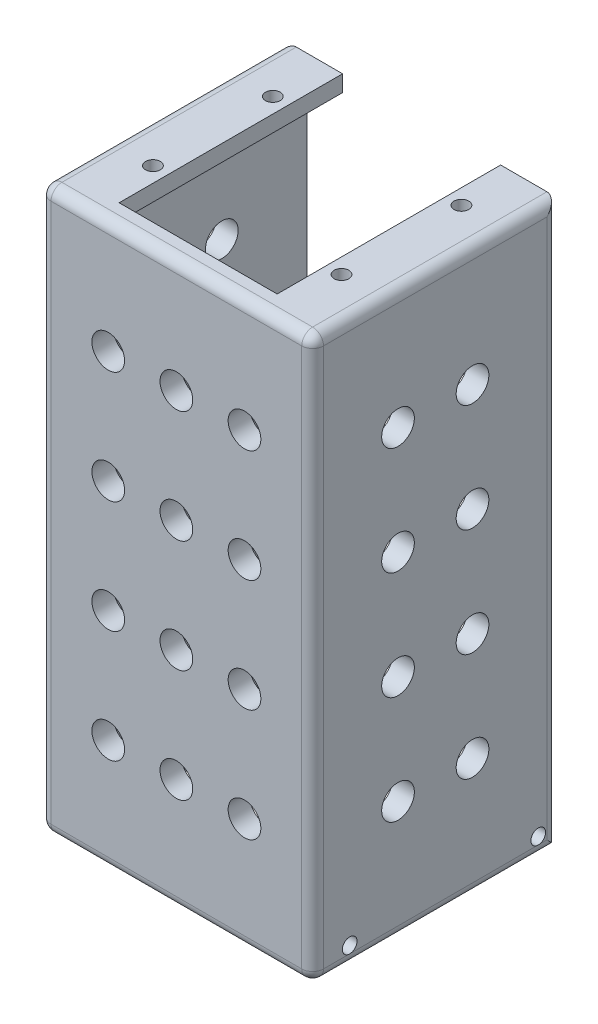
SolidWorks part; units mm, degrees
material "ABS PC"
ref_plane "Front Plane" through (0, 0, 0) normal (0, 0, 1) x (1, 0, 0)
ref_plane "Top Plane" through (0, 0, 0) normal (0, 1, 0) x (1, 0, 0)
ref_plane "Right Plane" through (0, 0, 0) normal (1, 0, 0) x (0, 0, -1)
sketch "Sketch2" plane through (0, 0, 0) normal (0, 1, 0) x (1, 0, 0)
  line L1 (25, -22.5) -> (-25, -22.5)
  line L2 (25, -22.5) -> (25, 22.5)
  line L3 (25, 22.5) -> (-25, 22.5)
  line L4 (-25, -22.5) -> (-25, 22.5)
  line L5 (25, -22.5) -> (-25, 22.5) construction
  line L6 (25, 22.5) -> (-25, -22.5) construction
  point P0 (0, 0)
extrude "Boss-Extrude1" add sketch "Sketch2" along normal blind 103
sketch "Sketch3" plane through (0, 103, 0) normal (0, 1, 0) x (1, 0, 0)
  line L0 (-21, 22.5) -> (-21, -18.5)
  line L1 (25, 22.5) -> (-25, 22.5) construction
  line L2 (-21, -18.5) -> (21, -18.5)
  line L3 (21, -18.5) -> (21, 22.5)
  line L4 (25, -22.5) -> (25, 22.5) construction
  line L5 (-25, 22.5) -> (-25, -22.5) construction
  line L6 (-25, -22.5) -> (25, -22.5) construction
  line L7 (-21, 22.5) -> (21, 22.5)
  dimension "D1" = 4
  dimension "D2" = 4
  dimension "D3" = 4
extrude "Cut-Extrude1" cut sketch "Sketch3" against normal blind 150
sketch "Sketch4" plane through (0, 103, 0) normal (0, 1, 0) x (1, 0, 0)
  line L0 (-25, -11.5) -> (-16, -11.5)
  line L1 (-25, 22.5) -> (-25, -22.5) construction
  line L2 (-16, -11.5) -> (-16, -6.5)
  line L3 (-16, -6.5) -> (-25, -6.5)
  line L4 (-25, -6.5) -> (-25, -11.5)
  line L5 (-21, -18.5) -> (21, -18.5) construction
  line L6 (-21, 22.5) -> (-21, -18.5) construction
  line L7 (0, -22.5) -> (0, 39.4349)
  line L8 (-25, -22.5) -> (25, -22.5) construction
  line L9 (25, -6.5) -> (25, -11.5)
  line L10 (25, -11.5) -> (16, -11.5)
  line L11 (16, -11.5) -> (16, -6.5)
  line L12 (16, -6.5) -> (25, -6.5)
  dimension "D1" = 7
  dimension "D2" = 12
  dimension "D3" = 5
extrude "Boss-Extrude4" [suppressed] add sketch "Sketch4" along normal blind 2 contours L2 L3 L4 L0 | L12 L9 L10 L11
sketch "Sketch6" plane through (0, 0, 22.5) normal (0, 0, 1) x (1, 0, 0)
  line L0 (-25, 103) -> (25, 103) construction
  line L1 (25, 103) -> (25, 0) construction
  circle A0 centre (12.5, 82.4) radius 3
  circle A1 centre (0, 82.4) radius 3
  circle A2 centre (-12.5, 82.4) radius 3
  circle A3 centre (-12.5, 61.8) radius 3
  circle A4 centre (0, 61.8) radius 3
  circle A5 centre (12.5, 61.8) radius 3
  circle A6 centre (12.5, 20.6) radius 3
  circle A7 centre (0, 20.6) radius 3
  circle A8 centre (-12.5, 20.6) radius 3
  circle A9 centre (-12.5, 41.2) radius 3
  circle A10 centre (0, 41.2) radius 3
  circle A11 centre (12.5, 41.2) radius 3
  dimension "D1" = 20.6
  dimension "D2" = 12.5
  dimension "D3" = 12.5
  dimension "D4" = 12.5
fillet "Fillet2" radius 2 7 edges at (0, 103, 22.5) (25, 51.5, 22.5) (0, 0, 22.5) (-25, 51.5, -22.5) (-25, 103, 0) (-25, 51.5, 22.5) (-25, 0, 0)
fillet "Fillet3" radius 2 5 edges at (24.4142, 0.5858, 21.9142) (24.4142, 102.4142, 21.9142) (25, 103, -1) (25, 51.5, -22.5) (25, 0, -1)
sketch "Sketch7" plane through (-21, 0, 0) normal (1, 0, 0) x (0, 0, -1)
  line L0 (-12.9, 0) -> (-12.9, 103)
  line L1 (22.5, 0) -> (-18.5, 0) construction
  line L2 (22.5, 103) -> (-18.5, 103) construction
  line L3 (-18.5, 0) -> (-18.5, 103) construction
  line L4 (16.1, 0) -> (16.1, 103)
  line L5 (21.7, 0) -> (21.7, 103)
  line L6 (-12.9, 103) -> (-18.5, 103)
  line L7 (-18.5, 103) -> (-18.5, 0)
  line L8 (-18.5, 0) -> (-29.6933, -0.9584)
  line L9 (-29.6933, -0.9584) -> (21.7, 0)
  line L10 (21.7, 103) -> (-18.5, 103)
  line L11 (-18.5, 30) -> (21.7, 30)
  line M9 (-18.5, 0) -> (22.5, 0)
  dimension "D1" = 5.6
  dimension "D2" = 29
  dimension "D3" = 5.6
  dimension "D4" = 1.068
  dimension "D5" = 30
extrude "Boss-Extrude6" add sketch "Sketch7" along normal blind 4 contours L11 L4 L5 M9 | L11 L7 L0 M9 region at (-21, 15, 15.7) region at (-21, 15, -18.9)
sketch "Sketch9" plane through (21, 0, 0) normal (-1, 0, 0) x (0, 0, 1)
  line L0 (12.9, 0) -> (12.9, 30)
  line L1 (18.5, 0) -> (-22.5, 0) construction
  line L2 (12.9, 30) -> (18.5, 30)
  line L3 (18.5, 0) -> (18.5, 103) construction
  line L4 (18.5, 30) -> (18.5, 0)
  line L5 (18.5, 0) -> (12.9, 0)
  line L6 (12.9, 0) -> (30.194, -0.1896)
  line L7 (-16.1, 0) -> (-16.1, 30)
  line L8 (-16.1, 30) -> (12.9, 30)
  line L9 (-16.1, 30) -> (-21.7, 30)
  line L10 (-21.7, 30) -> (-21.7, 0)
  line L11 (-21.7, 0) -> (-16.1, 0)
  line M5 (18.5, 0) -> (18.5, 103)
  line M10 (-22.5, 0) -> (18.5, 0)
  dimension "D1" = 5.6
  dimension "D2" = 29
  dimension "D3" = 5.6
  dimension "D4" = 30
extrude "Boss-Extrude7" add sketch "Sketch9" along normal blind 4 contours L9 L10 L7 M10 | L2 L0 M10 M5 region at (21, 15, 15.7) region at (21, 15, -18.9)
sketch "Sketch10" plane through (-17, 0, 0) normal (1, 0, 0) x (0, 0, -1)
  line L0 (18.9, 0) -> (18.9, 30)
  line L1 (16.1, 0) -> (21.7, 0) construction
  line L2 (16.1, 30) -> (21.7, 30) construction
  line L3 (18.9, 3.3485) -> (-18.5, 3.3485)
  line L4 (-18.5, 30) -> (-18.5, 0) construction
  line L5 (-15.7, 0) -> (-15.7, 3.3485)
  line L8 (-18.5, 0) -> (-12.9, 0) construction
  circle A0 centre (18.9, 3.3485) radius 1.35
  circle A1 centre (-15.7, 3.3485) radius 1.35
extrude "Cut-Extrude3" cut sketch "Sketch10" against normal through all both and the other way through all contours A0 | A1
sketch "Sketch12" plane through (-25, 0, 0) normal (-1, 0, 0) x (0, 0, 1)
  circle A0 centre (-6.84, 81.2) radius 3
  circle A1 centre (-6.84, 61.4) radius 3
  circle A2 centre (-6.84, 41.6) radius 3
  circle A3 centre (-6.84, 21.8) radius 3
  circle A4 centre (6.83, 21.8) radius 3
  circle A5 centre (6.83, 41.6) radius 3
  circle A6 centre (6.83, 61.4) radius 3
  circle A7 centre (6.83, 81.2) radius 3
extrude "Cut-Extrude5" cut sketch "Sketch12" against normal through all both and the other way through all
extrude "Cut-Extrude6" cut sketch "Sketch6" against normal through all
sketch "Sketch13" [suppressed] plane through (0, 103, 0) normal (0, -1, 0) x (1, 0, 0)
  line L0 (21, 11.5) -> (21, 6.5) construction
  circle A0 centre (18.2, 9) radius 1.35
  dimension "D1" = 2.7
  dimension "D2" = 2.8
extrude "Cut-Extrude7" [suppressed] cut sketch "Sketch13" against normal through all
sketch "Sketch14" plane through (0, 0, 18.5) normal (0, 0, -1) x (-1, 0, 0)
  line L0 (21, 30) -> (21, 103) construction
  line L1 (-21, 103) -> (21, 103)
  line L2 (-21, 103) -> (-21, 100)
  line L3 (-21, 100) -> (21, 100)
  line L4 (21, 103) -> (21, 100)
  dimension "D1" = 3
extrude "Boss-Extrude8" add sketch "Sketch14" along normal blind 41
sketch "Sketch16" plane through (0, 0, -22.5) normal (0, 0, -1) x (-1, 0, 0)
  line L0 (-23, 103) -> (23, 103) construction
  line L1 (-14.5, 103) -> (14.5, 103)
  line L2 (-14.5, 103) -> (-14.5, 100)
  line L3 (-14.5, 100) -> (14.5, 100)
  line L4 (14.5, 103) -> (14.5, 100)
  line L5 (-21, 100) -> (21, 100) construction
  dimension "D1" = 29
  dimension "D2" = 6.5
extrude "Cut-Extrude8" cut sketch "Sketch16" against normal blind 41
sketch "Sketch17" plane through (0, 103, 0) normal (0, 1, 0) x (1, 0, 0)
  line L0 (-14.5, -18.5) -> (14.5, -18.5) construction
  line L2 (14.5, -18.5) -> (14.5, 22.5) construction
  line L3 (-14.5, -18.5) -> (-14.5, 22.5) construction
  circle A0 centre (17.3, -9.5) radius 1.35
  circle A1 centre (-17.3, -9.5) radius 1.35
  dimension "D1" = 2.7
  dimension "D4" = 2.7
  dimension "D6" = 9
  dimension "D2" = 9
  dimension "D3" = 2.8
  dimension "D5" = 2.8
extrude "Cut-Extrude9" cut sketch "Sketch17" against normal blind 3
sketch "Sketch18" plane through (0, 103, 0) normal (0, 1, 0) x (1, 0, 0)
  line L0 (14.5, -18.5) -> (14.5, 22.5) construction
  line L1 (-14.5, -18.5) -> (-14.5, 22.5) construction
  circle A0 centre (17.3, 12.5) radius 1.35
  circle A1 centre (-17.3, 12.5) radius 1.35
  circle A2 centre (17.3, -9.5) radius 1.35 construction
  circle A3 centre (-17.3, -9.5) radius 1.35 construction
  dimension "D1" = 2.7
  dimension "D2" = 2.7
  dimension "D3" = 22
  dimension "D4" = 22
  dimension "D5" = 2.8
  dimension "D6" = 2.8
extrude "Cut-Extrude10" cut sketch "Sketch18" against normal blind 3
